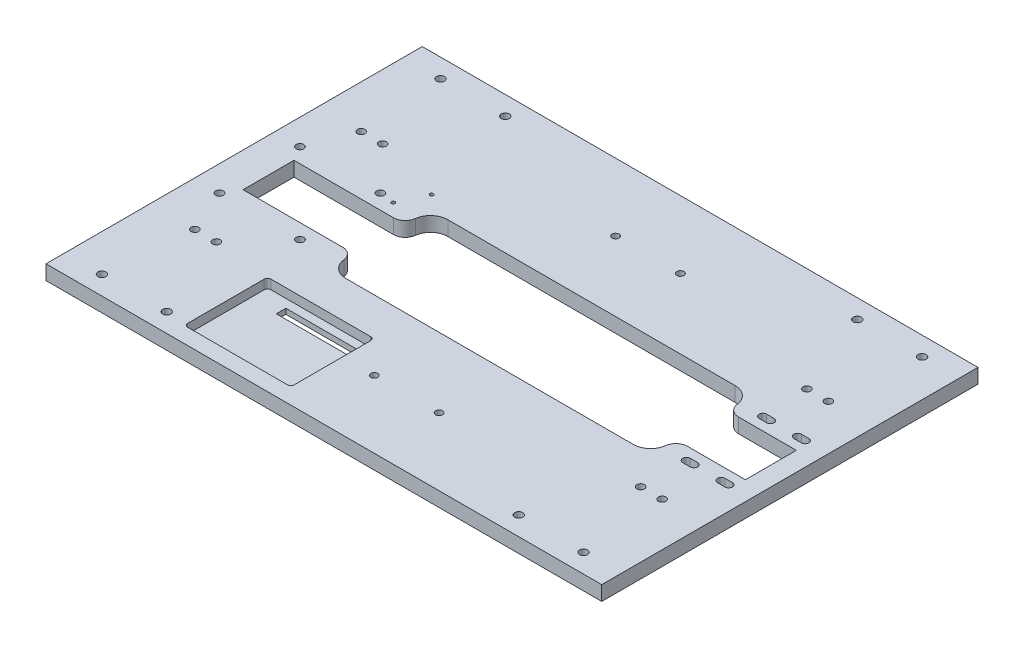
SolidWorks part; units mm, degrees
ref_plane "Front Plane" through (0, 0, 0) normal (0, 0, 1) x (1, 0, 0)
ref_plane "Top Plane" through (0, 0, 0) normal (0, 1, 0) x (1, 0, 0)
ref_plane "Right Plane" through (0, 0, 0) normal (1, 0, 0) x (0, 0, -1)
sketch "Sketch1" plane through (0, 0, 0) normal (0, 1, 0) x (1, 0, 0)
  line L1 (-240, 162.5) -> (240, 162.5)
  line L2 (-240, 162.5) -> (-240, -162.5)
  line L3 (-240, -162.5) -> (240, -162.5)
  line L4 (240, 162.5) -> (240, -162.5)
  line L5 (-240, 162.5) -> (240, -162.5) construction
  line L6 (-240, -162.5) -> (240, 162.5) construction
  point P0 (0, 0)
  dimension "D1" = 480
  dimension "D2" = 325
extrude "Boss-Extrude1" add sketch "Sketch1" along normal blind 12.6
sketch "Sketch2" plane through (0, 0, 0) normal (0, -1, 0) x (1, 0, 0)
  circle A0 centre (41.2474, -104.2) radius 3
  circle A1 centre (-14.7526, -104.2) radius 3
  circle A2 centre (41.2474, 104.2) radius 3
  circle A3 centre (-14.7526, 104.2) radius 3
extrude "Cut-Extrude1" cut sketch "Sketch2" against normal up to next
sketch "Sketch3" plane through (0, 0, 0) normal (0, -1, 0) x (1, 0, 0)
  line L0 (-192.4406, 0) -> (188.5847, 0) construction
  line L1 (163.5847, 44) -> (-114.2887, 44)
  line L2 (163.5847, 44) -> (163.5847, 22)
  line L3 (163.5847, -44) -> (-114.2887, -44)
  line L5 (-114.2887, -44) -> (-114.2887, -22)
  line L6 (-114.2887, -22) -> (-210.2887, -22)
  line L7 (-114.2887, 44) -> (-114.2887, 22)
  line L8 (-114.2887, 22) -> (-210.2887, 22)
  line L9 (-210.2887, 22) -> (-210.2887, -22)
  line L10 (163.5847, 22) -> (223.5847, 22)
  line L11 (223.5847, 22) -> (223.5847, -22)
  line L12 (223.5847, -22) -> (163.5847, -22)
  line L13 (163.5847, -22) -> (163.5847, -44)
  point P0 (0, 0)
  point P1 (-210.2887, 0)
  dimension "D2" = 96
  dimension "D1" = 22
  dimension "D5" = 60
extrude "Cut-Extrude2" cut sketch "Sketch3" against normal up to next
fillet "Fillet1" radius 10 2 edges at (-114.2887, 6.3, 22) (-114.2887, 6.3, -22)
sketch "Sketch4" plane through (0, 0, 0) normal (0, -1, 0) x (1, 0, 0)
  circle A12 centre (-148.4257, -34.75) radius 3.3
  circle A13 centre (-148.4257, 34.75) radius 3.3
  circle A14 centre (-217.9257, 34.75) radius 3.3
  circle A15 centre (-217.9257, -34.75) radius 3.3
  point P0 (0, 0)
  point P24 (0, 0)
  point P25 (0, 0)
  point P26 (0, 0)
  point P27 (0, 0)
  point P28 (0, 0)
  point P29 (0, 0)
  point P30 (0, 0)
  point P31 (0, 0)
extrude "Cut-Extrude3" cut sketch "Sketch4" against normal up to next
fillet "Fillet2" radius 10 2 edges at (163.5847, 6.3, -22) (163.5847, 6.3, 22)
sketch "Sketch7" plane through (0, 12.6, 0) normal (0, 1, 0) x (1, 0, 0)
  circle A0 centre (208, -146.2) radius 2.25
  circle A1 centre (152, -146.2) radius 2.25
  circle A2 centre (-152, -146.2) radius 2.25
  circle A3 centre (-208, -146.2) radius 2.25
  circle A4 centre (-208, 146.2) radius 2.25
  circle A5 centre (-152, 146.2) radius 2.25
  circle A6 centre (208, 146.2) radius 2.25
  circle A7 centre (152, 146.2) radius 2.25
  dimension "D1" = 4.5
extrude "Cut-Extrude7" cut sketch "Sketch7" against normal up to next
sketch "Sketch8" plane through (0, 12.6, 0) normal (0, 1, 0) x (1, 0, 0)
  circle A0 centre (208, 146.2) radius 3.5
  circle A1 centre (152, 146.2) radius 3.5
  circle A2 centre (-152, 146.2) radius 3.5
  circle A3 centre (-208, 146.2) radius 3.5
  circle A4 centre (208, -146.2) radius 3.5
  circle A5 centre (152, -146.2) radius 3.5
  circle A6 centre (-208, -146.2) radius 3.5
  circle A7 centre (-152, -146.2) radius 3.5
  dimension "D1" = 7
extrude "Cut-Extrude8" cut sketch "Sketch8" against normal blind 6
sketch "Sketch9" plane through (0, 12.6, 0) normal (0, 1, 0) x (1, 0, 0)
  line L1 (-131.2752, -76.7932) -> (-45.2752, -76.7932)
  line L2 (-134.2752, -79.7932) -> (-134.2752, -145.7932)
  line L3 (-131.2752, -148.7932) -> (-45.2752, -148.7932)
  line L4 (-42.2752, -79.7932) -> (-42.2752, -145.7932)
  arc A0 (-134.2752, -145.7932) -> (-131.2752, -148.7932) centre (-131.2752, -145.7932) ccw
  arc A1 (-45.2752, -148.7932) -> (-42.2752, -145.7932) centre (-45.2752, -145.7932) ccw
  arc A2 (-45.2752, -76.7932) -> (-42.2752, -79.7932) centre (-45.2752, -79.7932) cw
  arc A3 (-131.2752, -76.7932) -> (-134.2752, -79.7932) centre (-131.2752, -79.7932) ccw
  dimension "D5" = 3
sketch "Sketch12" plane through (0, 0, 0) normal (0, -1, 0) x (1, 0, 0)
  circle A0 centre (-135.8148, -33.2631) radius 1.5
  circle A1 centre (-125.2148, -55.8631) radius 1.5
extrude "Cut-Extrude11" cut sketch "Sketch12" against normal up to next
fillet "Fillet3" radius 15 4 edges at (163.5847, 6.3, 44) (163.5847, 6.3, -44) (-114.2887, 6.3, 44) (-114.2887, 6.3, -44)
extrude "Cut-Extrude12" cut sketch "Sketch9" against normal blind 8
sketch "Sketch14" plane through (0, 4.6, 0) normal (0, 1, 0) x (1, 0, 0)
  line L1 (-111.1572, -84.1633) -> (-47.573, -84.1633)
  line L2 (-111.1572, -84.1633) -> (-111.1572, -92.4204)
  line L3 (-111.1572, -92.4204) -> (-47.573, -92.4204)
  line L4 (-47.573, -84.1633) -> (-47.573, -92.4204)
extrude "Cut-Extrude13" cut sketch "Sketch14" against normal through all
sketch "Sketch15" plane through (0, 12.6, 0) normal (0, 1, 0) x (1, 0, 0)
  circle A0 centre (-201.3752, -72.5) radius 3.25 construction
  circle A1 centre (-182.8647, -72.5) radius 3.25 construction
  circle A2 centre (-202.7941, 72.5123) radius 3.25 construction
  circle A3 centre (-184.2837, 72.5123) radius 3.25 construction
  circle A4 centre (182.2059, 72.5) radius 3.25 construction
  circle A5 centre (200.7163, 72.5) radius 3.25 construction
  circle A6 centre (183.6248, -72.5) radius 3.25 construction
  circle A7 centre (202.1353, -72.5) radius 3.25 construction
  circle A8 centre (-201.3752, -72.5) radius 3.25
  circle A9 centre (-182.8647, -72.5) radius 3.25
  circle A10 centre (-202.7941, 72.5123) radius 3.25
  circle A11 centre (-184.2837, 72.5123) radius 3.25
  circle A12 centre (182.2059, 72.5) radius 3.25
  circle A13 centre (200.7163, 72.5) radius 3.25
  circle A14 centre (183.6248, -72.5) radius 3.25
  circle A15 centre (202.1353, -72.5) radius 3.25
extrude "Cut-Extrude14" cut sketch "Sketch15" against normal up to next
sketch "Sketch16" plane through (0, 12.6, 0) normal (0, 1, 0) x (1, 0, 0)
  line L0 (183.6729, -33) -> (186.9229, -33) construction
  line L1 (213.6729, -33) -> (216.9229, -33) construction
  line L2 (183.6729, 33) -> (186.9229, 33) construction
  line L3 (213.6729, 33) -> (216.9229, 33) construction
  line L4 (183.6729, -36.25) -> (190.1729, -36.25)
  line L5 (183.6729, -29.75) -> (190.1729, -29.75)
  line L6 (213.6729, -36.25) -> (220.1729, -36.25)
  line L7 (213.6729, -29.75) -> (220.1729, -29.75)
  line L8 (183.6729, 29.75) -> (190.1729, 29.75)
  line L9 (183.6729, 36.25) -> (190.1729, 36.25)
  line L10 (213.6729, 29.75) -> (220.1729, 29.75)
  line L11 (213.6729, 36.25) -> (220.1729, 36.25)
  arc A4 (213.6729, -29.75) -> (213.6729, -36.25) centre (213.6729, -33) ccw
  arc A5 (183.6729, -29.75) -> (183.6729, -36.25) centre (183.6729, -33) ccw
  arc A6 (183.6729, 36.25) -> (183.6729, 29.75) centre (183.6729, 33) ccw
  arc A7 (213.6729, 36.25) -> (213.6729, 29.75) centre (213.6729, 33) ccw
  arc A8 (190.1729, -36.25) -> (190.1729, -29.75) centre (190.1729, -33) ccw
  arc A9 (220.1729, -36.25) -> (220.1729, -29.75) centre (220.1729, -33) ccw
  arc A10 (220.1729, 29.75) -> (220.1729, 36.25) centre (220.1729, 33) ccw
  arc A11 (190.1729, 29.75) -> (190.1729, 36.25) centre (190.1729, 33) ccw
  dimension "D1" = 6.5
  dimension "D2" = 6.5
  dimension "D3" = 6.5
  dimension "D4" = 6.5
extrude "Cut-Extrude15" cut sketch "Sketch16" against normal up to next
